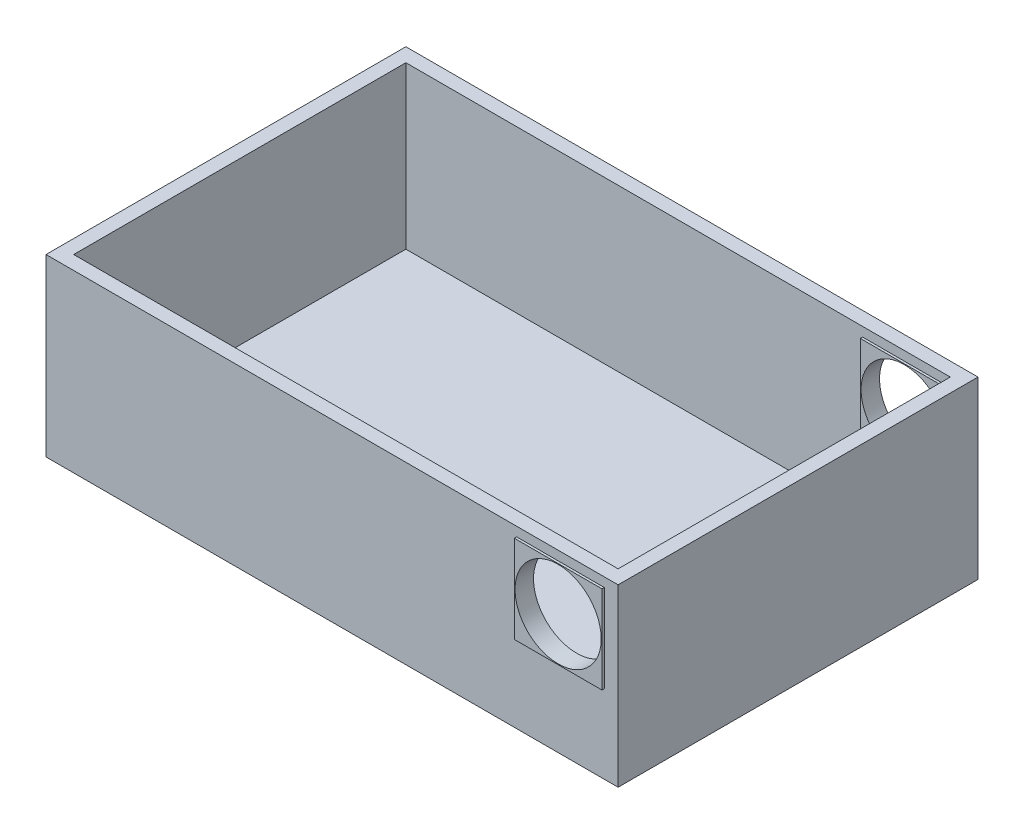
SolidWorks part; units mm, degrees
ref_plane "Front Plane" through (0, 0, 0) normal (0, 0, 1) x (1, 0, 0)
ref_plane "Top Plane" through (0, 0, 0) normal (0, 1, 0) x (1, 0, 0)
ref_plane "Right Plane" through (0, 0, 0) normal (1, 0, 0) x (0, 0, -1)
sketch "Sketch1" plane through (0, 0, 0) normal (0, 1, 0) x (1, 0, 0)
  line L1 (0, 0) -> (787.4, 0)
  line L2 (0, 0) -> (0, 495.3)
  line L3 (0, 495.3) -> (787.4, 495.3)
  line L4 (787.4, 0) -> (787.4, 495.3)
  dimension "D1" = 787.4
  dimension "D2" = 495.3
extrude "Boss-Extrude1" add sketch "Sketch1" along normal blind 241.3
shell "Shell1" thickness 19.05 removed face at (393.7, 241.3, -247.65)
sketch "Sketch2" plane through (0, 0, 0) normal (0, 0, 1) x (1, 0, 0)
  line L0 (787.4, 241.3) -> (787.4, 0) construction
  line L1 (768.35, 228.6) -> (647.7, 228.6)
  line L2 (768.35, 228.6) -> (768.35, 107.95)
  line L3 (768.35, 107.95) -> (647.7, 107.95)
  line L4 (647.7, 228.6) -> (647.7, 107.95)
  line L10 (0, 241.3) -> (787.4, 241.3) construction
  dimension "D1" = 120.65
  dimension "D2" = 120.65
  dimension "D3" = 19.05
  dimension "D4" = 12.7
extrude "Boss-Extrude2" add sketch "Sketch2" along normal blind 3.175 and the other way blind 22.225 contours L1 L4 L3 L2
sketch "Sketch3" plane through (0, 0, 3.175) normal (0, 0, 1) x (1, 0, 0)
  line L0 (647.7, 228.6) -> (768.35, 228.6) construction
  line L1 (768.35, 228.6) -> (768.35, 107.95) construction
  line L2 (768.35, 228.6) -> (768.35, 107.95) construction
  line L3 (768.35, 107.95) -> (647.7, 107.95) construction
  line L4 (647.7, 107.95) -> (647.7, 228.6) construction
  line L5 (708.025, 107.95) -> (708.025, 228.6) construction
  line L6 (647.7, 168.275) -> (768.35, 168.275) construction
  circle A1 centre (708.025, 168.275) radius 59.309
  dimension "D1" = 118.618
extrude "Cut-Extrude2" cut sketch "Sketch3" against normal blind 25.4
ref_plane "Plane1" through (0, 0, -247.65) normal (0, 0, 1) x (1, 0, 0)
mirror "Mirror1" about plane through (0, 0, -247.65) normal (0, 0, 1) of "Cut-Extrude2", "Boss-Extrude2"
